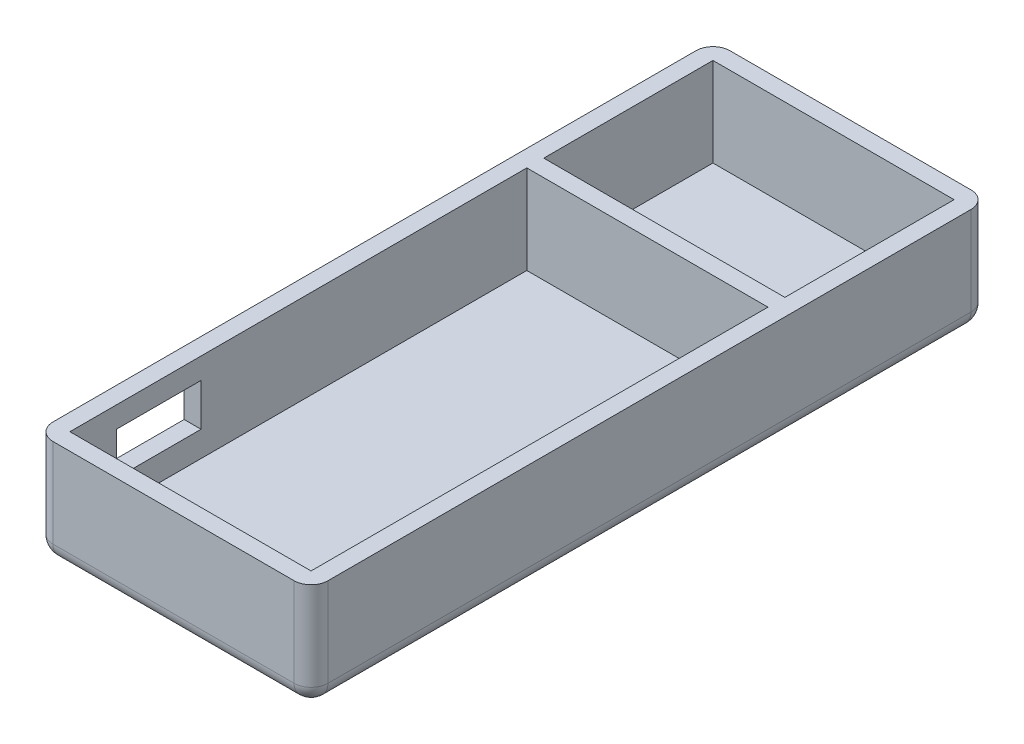
SolidWorks part; units mm, degrees
ref_plane "Front Plane" through (0, 0, 0) normal (0, 0, 1) x (1, 0, 0)
ref_plane "Top Plane" through (0, 0, 0) normal (0, 1, 0) x (1, 0, 0)
ref_plane "Right Plane" through (0, 0, 0) normal (1, 0, 0) x (0, 0, -1)
sketch "Sketch2" plane through (0, 0, 0) normal (0, 1, 0) x (1, 0, 0)
  line L0 (-32.5, 80) -> (32.5, -80) construction
  line L1 (-32.5, 80) -> (32.5, 80)
  line L2 (-32.5, 80) -> (-32.5, -80)
  line L3 (-32.5, -80) -> (32.5, -80)
  line L4 (32.5, 80) -> (32.5, -80)
  line L5 (-32.5, -80) -> (32.5, 80) construction
  point P4 (0, 0)
  dimension "D1" = 65
  dimension "D2" = 160
extrude "Base" add sketch "Sketch2" along normal blind 25
sketch "Sketch3" plane through (0, 25, 0) normal (0, 1, 0) x (1, 0, 0)
  line L0 (32.5, -80) -> (32.5, 80) construction
  line L1 (-28.5, -76) -> (28.5, -76)
  line L2 (-28.5, -76) -> (-28.5, 76)
  line L3 (-28.5, 76) -> (28.5, 76)
  line L4 (28.5, -76) -> (28.5, 76)
  line L5 (-28.5, -76) -> (28.5, 76) construction
  line L6 (-28.5, 76) -> (28.5, -76) construction
  line L7 (32.5, 80) -> (-32.5, 80) construction
  point P0 (0, 0)
  dimension "D1" = 4
  dimension "D2" = 4
extrude "Inside Space" cut sketch "Sketch3" against normal offset from surface (21 mm away) 4 up to face at (0, 0, 0)
sketch "Sketch4" plane through (0, 4, 0) normal (0, 1, 0) x (1, 0, 0)
  line L0 (-28.5, 76) -> (-28.5, -76) construction
  line L1 (-28.5, 36) -> (28.5, 36)
  line L2 (-28.5, 36) -> (-28.5, 32)
  line L3 (-28.5, 32) -> (28.5, 32)
  line L4 (28.5, 36) -> (28.5, 32)
  line L5 (28.5, -76) -> (28.5, 76) construction
  line L6 (-28.5, 76) -> (28.5, 76) construction
  dimension "D1" = 40
  dimension "D2" = 4
extrude "Battery Wall" add sketch "Sketch4" along normal up to surface (21 mm away) up to face at (0, 25, 0)
sketch "Sketch6" plane through (-32.5, 0, 0) normal (-1, 0, 0) x (0, 0, 1)
  line L0 (-80, 0) -> (80, 0) construction
  line L1 (65, 20) -> (45, 20)
  line L2 (65, 20) -> (65, 10)
  line L3 (65, 10) -> (45, 10)
  line L4 (45, 20) -> (45, 10)
  line L5 (80, 25) -> (80, 0) construction
  dimension "D1" = 20
  dimension "D2" = 10
  dimension "D3" = 10
  dimension "D4" = 15
extrude "Connector Hole" cut sketch "Sketch6" against normal up to surface (4 mm away) up to face at (-28.5, 14.5, 22)
fillet "Rounding" radius 4 8 edges at (0, 0, 80) (32.5, 12.5, 80) (-32.5, 12.5, 80) (-32.5, 0, 0) (-32.5, 12.5, -80) (0, 0, -80) (32.5, 0, 0) (32.5, 12.5, -80)
